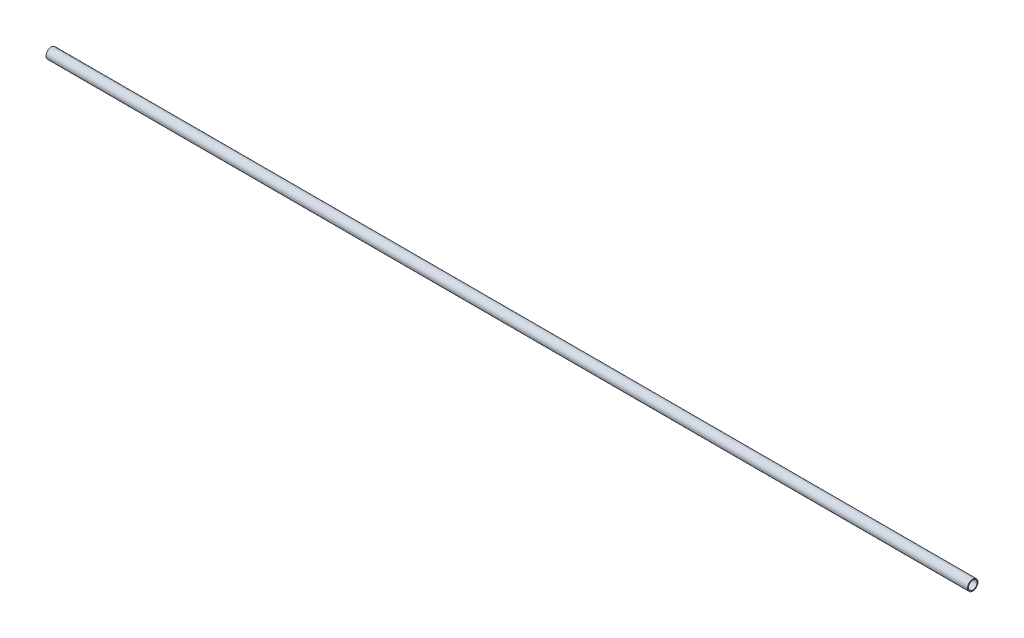
SolidWorks part; units mm, degrees
ref_plane "Front Plane" through (0, 0, 0) normal (0, 0, 1) x (1, 0, 0)
ref_plane "Top Plane" through (0, 0, 0) normal (0, 1, 0) x (1, 0, 0)
ref_plane "Right Plane" through (0, 0, 0) normal (1, 0, 0) x (0, 0, -1)
ref_axis "Axis1" through (-88.99, 0, 0) along (1, 0, 0)
sketch "Sketch1" plane through (0, 0, 0) normal (1, 0, 0) x (0, 0, -1)
  circle A0 centre (0, 0) radius 0.5143
  circle A1 centre (0, 0) radius 0.6223
  dimension "D1" = 1.0287
  dimension "D2" = 1.2446
extrude "Boss-Extrude1" add sketch "Sketch1" along normal blind 110
sketch "Sketch2" plane through (0, 0, 0) normal (0, 0, 1) x (1, 0, 0)
  line L0 (482.41, -312.5888) -> (76.41, -312.5888) construction
  line L1 (110, -0.6223) -> (110, 0.6223) construction
  line L2 (110, -0.6223) -> (110, 0.6223) construction
  line L3 (-108.0952, 5.0944) -> (-101.3653, 6.437)
  line L4 (-102.5187, 8.6259) -> (-98.3985, 14.7997) construction
  line L5 (-98.3985, 14.7997) -> (-102.5187, 8.6259) construction
  line L6 (-102.5187, 8.6259) -> (-117.379, 5.6615) construction
  line L7 (-102.7617, 10.1061) -> (-102.2758, 7.1457) construction
  line L8 (-107.9735, 4.4842) -> (-101.0235, 5.8706)
  line L9 (-108.217, 5.7047) -> (-101.7361, 6.9976)
  arc A0 (110, 0) -> (109.6499, 2.3233) centre (109.3479, 1.0898) ccw
  arc A1 (-101.3653, 6.437) -> (-101.5167, 10.1273) centre (-103.6943, 8.1897) ccw
  arc A2 (-101.0235, 5.8706) -> (-101.0518, 10.541) centre (-103.6943, 8.1897) ccw
  arc A3 (-101.7361, 6.9976) -> (-101.9816, 9.7137) centre (-103.6943, 8.1897) ccw
  arc A4 (-101.3653, 6.437) -> (-100.1777, 12.1338) centre (-102.3611, 9.6168) ccw
  arc A5 (-101.1793, 5.8431) -> (-99.6269, 12.4735) centre (-102.3611, 9.6168) ccw
  arc A6 (-101.5512, 7.0309) -> (-100.4874, 11.5744) centre (-102.3611, 9.6168) ccw
  arc A7 (-101.3653, 6.437) -> (-100.0572, 12.024) centre (-102.3611, 9.6168) ccw construction
  point P2 (110, 0)
  point P6 (110, 0)
  point P18 (-102.5187, 8.6259)
  dimension "D1" = 1.27
  dimension "D3" = 3
  dimension "D9" = 0.6223
  dimension "D2" = 3
  dimension "D4" = 45
  dimension "D5" = 4
  dimension "D8" = 1.75
  dimension "D6" = 0.6223
  dimension "D7" = 0.6223
  dimension "D10" = 0.6223
sketch "Sketch3" plane through (110, 0, 0) normal (1, 0, 0) x (0, 0, -1)
  circle A1 centre (0, 0) radius 0.6223 construction
  circle A2 centre (0, 0) radius 0.5143 construction
  circle A3 centre (0, 0) radius 0.6223
  circle A4 centre (0, 0) radius 0.5143
sweep "Sweep1" add profiles "Sketch3" path "Sketch2" rebuild error yes
sketch "Sketch4" plane through (0, 0, 0) normal (0, 0, 1) x (1, 0, 0)
  line L0 (110.0873, 2.766) -> (110, -0.6223)
